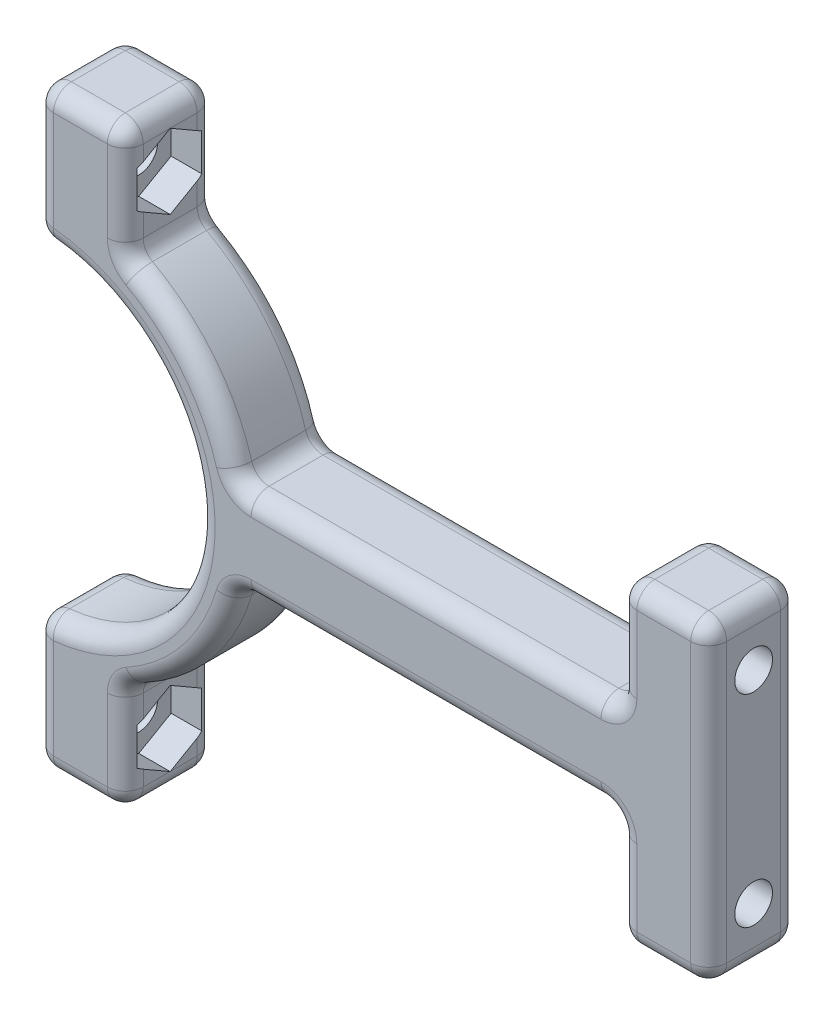
SolidWorks part; units mm, degrees
ref_plane "Front Plane" through (0, 0, 0) normal (0, 0, 1) x (1, 0, 0)
ref_plane "Top Plane" through (0, 0, 0) normal (0, 1, 0) x (1, 0, 0)
ref_plane "Right Plane" through (0, 0, 0) normal (1, 0, 0) x (0, 0, -1)
sketch "Sketch1" plane through (0, 0, 0) normal (0, 0, 1) x (1, 0, 0)
  line L0 (0, 18) -> (0, 23)
  line L1 (0, -18) -> (0, -23)
  arc A0 (0, -18) -> (0, 18) centre (0, 0) ccw
  arc A1 (0, -23) -> (0, 23) centre (0, 0) ccw
  circle A2 centre (0, 0) radius 23 construction
  circle A3 centre (0, 0) radius 18 construction
  dimension "D1" = 36
  dimension "D2" = 5
extrude "Boss-Extrude1" add sketch "Sketch1" along normal blind 10
ref_plane "Plane1" through (0, -23, 0) normal (0, -1, 0) x (-1, 0, 0)
sketch "Sketch2" plane through (0, -23, 0) normal (0, -1, 0) x (-1, 0, 0)
  line L0 (-23, -10) -> (0, -10) construction
  line L1 (0, 0) -> (-10, 0)
  line L2 (0, 0) -> (0, -10)
  line L3 (0, -10) -> (-10, -10)
  line L4 (-10, 0) -> (-10, -10)
  line L5 (0, 0) -> (-10, -10) construction
  line L6 (0, -10) -> (-10, 0) construction
  point P4 (-5, -5)
  dimension "D1" = 10
extrude "Boss-Extrude2" add sketch "Sketch2" along normal blind 10 and the other way up to surface other way up to face at (11.5, 0, 5)
sketch "Sketch4" plane through (10, 0, 0) normal (1, 0, 0) x (0, 0, -1)
  line L0 (0, -26.8562) -> (-10, -26.8562) construction
  line L1 (0, -20.7123) -> (0, -33) construction
  line L2 (-10, -20.7123) -> (-10, -33) construction
  circle A0 centre (-5, -26.8562) radius 2.1
  dimension "D1" = 4.2
extrude "Cut-Extrude2" cut sketch "Sketch4" against normal blind 10
sketch "Sketch5" plane through (10, 0, 0) normal (1, 0, 0) x (0, 0, -1)
  line L0 (0, -20.7123) -> (0, -33) construction
  line L1 (-1.4, -24.7777) -> (-5, -22.6992)
  line L2 (-5, -22.6992) -> (-8.6, -24.7777)
  line L3 (-8.6, -24.7777) -> (-8.6, -28.9346)
  line L4 (-8.6, -28.9346) -> (-5, -31.0131)
  line L5 (-5, -31.0131) -> (-1.4, -28.9346)
  line L6 (-1.4, -28.9346) -> (-1.4, -24.7777)
  circle A0 centre (-5, -26.8562) radius 3.6 construction
  dimension "D1" = 7.2
extrude "Cut-Extrude3" cut sketch "Sketch5" against normal blind 3.5
sketch "Sketch6" plane through (0, 0, 0) normal (0, 0, -1) x (-1, 0, 0)
  line L0 (0, 0) -> (-45.1438, 0) construction
  line L2 (-22.4499, 5) -> (-74.9499, 5)
  line L3 (-22.4499, 5) -> (-22.4499, -5)
  line L4 (-22.4499, -5) -> (-74.9499, -5)
  line L5 (-74.9499, 5) -> (-74.9499, -5)
  line L6 (-22.4499, 5) -> (-74.9499, -5) construction
  line L7 (-22.4499, -5) -> (-74.9499, 5) construction
  arc A0 (0, 23) -> (-10, -20.7123) centre (0, 0) ccw construction
  point P7 (-48.6999, 0)
  dimension "D1" = 5
  dimension "D2" = 5
  dimension "D3" = 52.5
extrude "Boss-Extrude3" add sketch "Sketch6" against normal up to surface (10 mm away) up to face at (9.2368, -9.9545, 10)
sketch "Sketch8" plane through (0, -5, 0) normal (0, -1, 0) x (1, 0, 0)
  line L0 (74.9499, 10) -> (22.4499, 10) construction
  line L1 (74.9499, 0) -> (64.9499, 0)
  line L2 (74.9499, 0) -> (74.9499, 10)
  line L3 (74.9499, 10) -> (64.9499, 10)
  line L4 (64.9499, 0) -> (64.9499, 10)
  line L5 (74.9499, 0) -> (64.9499, 10) construction
  line L6 (74.9499, 10) -> (64.9499, 0) construction
  point P4 (69.9499, 5)
  dimension "D1" = 10
extrude "Boss-Extrude4" add sketch "Sketch8" along normal blind 12.5
sketch "Sketch9" plane through (64.9499, 0, 0) normal (-1, 0, 0) x (0, 0, 1)
  line L0 (0, -11.25) -> (10, -11.25) construction
  line L1 (0, -17.5) -> (0, -5) construction
  line L2 (10, -17.5) -> (10, -5) construction
  circle A0 centre (5, -11.25) radius 2.1
  dimension "D1" = 4.2
extrude "Cut-Extrude4" cut sketch "Sketch9" against normal blind 12.5
sketch "Sketch10" plane through (64.9499, 0, 0) normal (-1, 0, 0) x (0, 0, 1)
  line L0 (0, -17.5) -> (0, -5) construction
  line L1 (1.4, -9.1715) -> (1.4, -13.3285)
  line L2 (1.4, -13.3285) -> (5, -15.4069)
  line L3 (5, -15.4069) -> (8.6, -13.3285)
  line L4 (8.6, -13.3285) -> (8.6, -9.1715)
  line L5 (8.6, -9.1715) -> (5, -7.0931)
  line L6 (5, -7.0931) -> (1.4, -9.1715)
  circle A0 centre (5, -11.25) radius 3.6 construction
  point P11 (8.6, -11.25)
  dimension "D1" = 7.2
extrude "Cut-Extrude5" cut sketch "Sketch10" against normal blind 3.5
mirror "Mirror1" about plane through (0, 0, 0) normal (0, 1, 0) of "Boss-Extrude2", "Cut-Extrude2", "Cut-Extrude3", "Boss-Extrude4", "Cut-Extrude4", "Cut-Extrude5"
fillet "Fillet1" radius 2 16 edges at (10, 20.7123, 5) (22.4499, 5, 5) (64.9499, 5, 5) (64.9499, 17.5, 5) (74.9499, 17.5, 5) (74.9499, -17.5, 5) (64.9499, -17.5, 5) (64.9499, -5, 5) (22.4499, -5, 5) (10, -20.7123, 5) (10, 33, 5) (0, 33, 5) (0, 18, 5) (0, -18, 5) (10, -33, 5) (0, -33, 5)
fillet "Fillet2" radius 2 64 edges at (10.2795, -20.9119, 10) (10, -26.4659, 10) (9.4142, -32.4142, 10) (5, -33, 10) (0.5858, -32.4142, 10) (0, -25.4499, 10) (0.5168, -18.5581, 10) (18, 0, 10) (0.5168, 18.5581, 10) (0, 25.4499, 10) (0.5858, 32.4142, 10) (5, 33, 10) (9.4142, 32.4142, 10) (10, 26.4659, 10) (10.2795, 20.9119, 10) (17.9279, 14.4079, 10) (22.8, 5.4, 10) (43.475, 5, 10) (64.3642, 5.5858, 10) (64.9499, 11.25, 10) (65.5357, 16.9142, 10) (69.9499, 17.5, 10) (74.3642, 16.9142, 10) (74.9499, 0, 10) (74.3642, -16.9142, 10) (69.9499, -17.5, 10) (65.5357, -16.9142, 10) (64.9499, -11.25, 10) (64.3642, -5.5858, 10) (43.475, -5, 10) (22.8, -5.4, 10) (64.3642, -5.5858, 0) (64.9499, -11.25, 0) (65.5357, -16.9142, 0) (69.9499, -17.5, 0) (74.3642, -16.9142, 0) (74.9499, 0, 0) (74.3642, 16.9142, 0) (69.9499, 17.5, 0) (65.5357, 16.9142, 0) (64.9499, 11.25, 0) (64.3642, 5.5858, 0) (43.475, 5, 0) (22.8, 5.4, 0) (17.9279, 14.4079, 0) (10.2795, 20.9119, 0) (10, 26.4659, 0) (9.4142, 32.4142, 0) (5, 33, 0) (0.5858, 32.4142, 0) (0, 25.4499, 0) (0.5168, 18.5581, 0) (18, 0, 0) (0.5168, -18.5581, 0) (0, -25.4499, 0) (0.5858, -32.4142, 0) (5, -33, 0) (9.4142, -32.4142, 0) (10, -26.4659, 0) (10.2795, -20.9119, 0) (17.9279, -14.4079, 0) (22.8, -5.4, 0) (17.9279, -14.4079, 10) (43.475, -5, 0)
